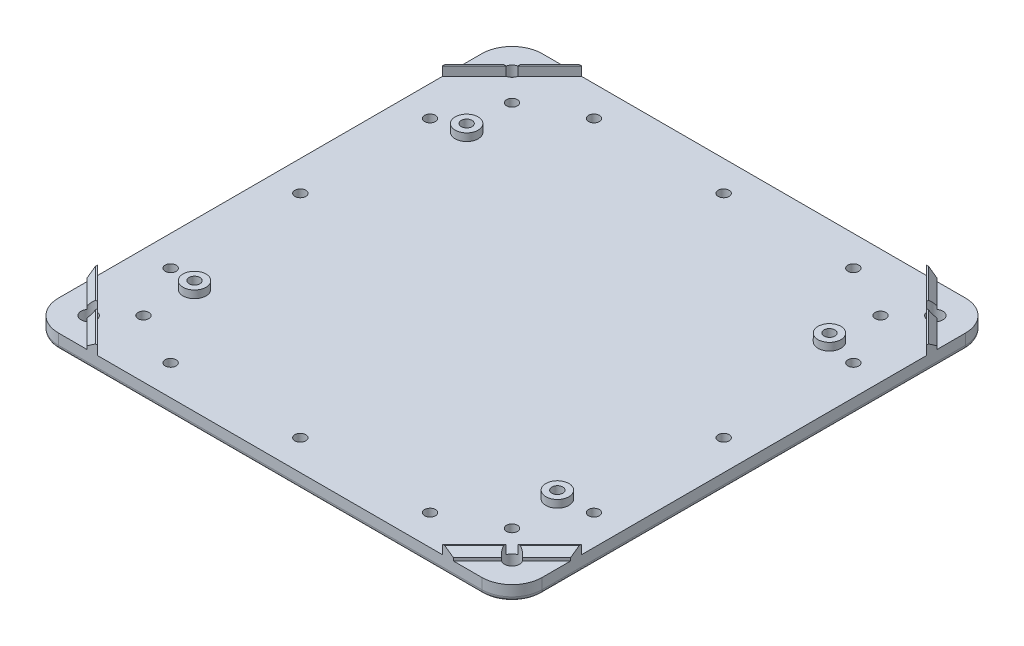
SolidWorks part; units mm, degrees
ref_plane "Front Plane" through (0, 0, 0) normal (0, 0, 1) x (1, 0, 0)
ref_plane "Top Plane" through (0, 0, 0) normal (0, 1, 0) x (1, 0, 0)
ref_plane "Right Plane" through (0, 0, 0) normal (1, 0, 0) x (0, 0, -1)
sketch "Sketch1" plane through (0, 0, 0) normal (0, 1, 0) x (1, 0, 0)
  line L1 (0, 0) -> (203.2, 0)
  line L2 (0, 0) -> (0, 203.2)
  line L3 (0, 203.2) -> (203.2, 203.2)
  line L4 (203.2, 0) -> (203.2, 203.2)
  dimension "D1" = 203.2
  dimension "D2" = 203.2
extrude "Boss-Extrude1" add sketch "Sketch1" along normal blind 6.35
fillet "Fillet1" radius 12.7 4 edges at (0, 3.175, -203.2) (0, 3.175, 0) (203.2, 3.175, 0) (203.2, 3.175, -203.2)
sketch "Sketch2" plane through (0, 0, 0) normal (0, -1, 0) x (1, 0, 0)
  circle A0 centre (12.7, -12.7) radius 3.175
  circle A1 centre (190.5, -12.7) radius 3.175
  circle A2 centre (190.5, -190.5) radius 3.175
  circle A3 centre (12.7, -190.5) radius 3.175
  arc A4 (190.5, -203.2) -> (203.2, -190.5) centre (190.5, -190.5) ccw construction
  arc A5 (12.7, 0) -> (0, -12.7) centre (12.7, -12.7) ccw construction
  arc A6 (12.7, 0) -> (0, -12.7) centre (12.7, -12.7) ccw construction
  dimension "D1" = 6.35
  dimension "D2" = 9.525
extrude "Cut-Extrude1" cut sketch "Sketch2" against normal through all
fillet "Fillet2" radius 1.905 12 edges at (3.7197, 0, -3.7197) (101.6, 0, 0) (199.4803, 0, -3.7197) (203.2, 0, -101.6) (199.4803, 0, -199.4803) (101.6, 0, -203.2) (3.7197, 0, -199.4803) (0, 0, -101.6) (12.7, 0, -15.875) (190.5, 0, -15.875) (190.5, 0, -193.675) (12.7, 0, -193.675)
sketch "Sketch3" plane through (0, 6.35, 0) normal (0, 1, 0) x (1, 0, 0)
  line L0 (3.7197, 3.7197) -> (24.1978, 24.1978) construction
  line L1 (24.1978, 24.1978) -> (0, 24.1978) construction
  line L2 (0, 190.5) -> (0, 12.7) construction
  line L3 (24.1978, 24.1978) -> (24.1978, 0) construction
  line L4 (12.7, 0) -> (190.5, 0) construction
  line L5 (3.7197, 199.4803) -> (24.1978, 179.0022) construction
  line L6 (0, 179.0022) -> (24.1978, 179.0022) construction
  line L7 (24.1978, 179.0022) -> (24.1978, 203.2) construction
  line L8 (190.5, 203.2) -> (12.7, 203.2) construction
  line L9 (199.4803, 3.7197) -> (179.0022, 24.1978) construction
  line L10 (179.0022, 24.1978) -> (179.0022, 0) construction
  line L12 (179.0022, 24.1978) -> (203.2, 24.1978) construction
  line L13 (203.2, 12.7) -> (203.2, 190.5) construction
  line L14 (199.4803, 199.4803) -> (179.0022, 179.0022) construction
  line L15 (179.0022, 179.0022) -> (203.2, 179.0022) construction
  line L16 (179.0022, 179.0022) -> (179.0022, 203.2) construction
  arc A0 (0, 12.7) -> (12.7, 0) centre (12.7, 12.7) ccw construction
  circle A1 centre (24.1978, 24.1978) radius 2.286
  arc A2 (190.5, 0) -> (203.2, 12.7) centre (190.5, 12.7) ccw construction
  arc A3 (203.2, 190.5) -> (190.5, 203.2) centre (190.5, 190.5) ccw construction
  arc A10 (12.7, 203.2) -> (0, 190.5) centre (12.7, 190.5) ccw construction
  circle A13 centre (179.0022, 179.0022) radius 2.286
  circle A14 centre (179.0022, 24.1978) radius 2.286
  circle A15 centre (24.1978, 179.0022) radius 2.286
  point P20 (101.6, 101.6)
  dimension "D2" = 4.572
  dimension "D1" = 28.9603
extrude "Cut-Extrude2" cut sketch "Sketch3" against normal through all
sketch "Sketch4" plane through (0, 6.35, 0) normal (0, 1, 0) x (1, 0, 0)
  line L0 (0, 190.5) -> (0, 12.7) construction
  line L1 (203.2, 12.7) -> (203.2, 190.5) construction
  line L2 (12.7, 0) -> (190.5, 0) construction
  line L3 (3.7197, 3.7197) -> (199.4803, 199.4803) construction
  circle A0 centre (47.117, 12.7) radius 2.286
  circle A1 centre (156.083, 12.7) radius 2.286
  arc A2 (0, 12.7) -> (12.7, 0) centre (12.7, 12.7) ccw construction
  arc A3 (203.2, 190.5) -> (190.5, 203.2) centre (190.5, 190.5) ccw construction
  circle A4 centre (12.7, 156.083) radius 2.286
  circle A5 centre (12.7, 47.117) radius 2.286
  circle A6 centre (156.083, 190.5) radius 2.286
  circle A7 centre (47.117, 190.5) radius 2.286
  circle A8 centre (190.5, 47.117) radius 2.286
  circle A9 centre (190.5, 156.083) radius 2.286
  circle A10 centre (101.6, 12.7) radius 2.286
  circle A11 centre (12.7, 101.6) radius 2.286
  circle A12 centre (101.6, 190.5) radius 2.286
  circle A13 centre (190.5, 101.6) radius 2.286
  point P18 (101.6, 101.6)
  dimension "D4" = 4.572
  dimension "D1" = 47.117
  dimension "D2" = 47.117
  dimension "D3" = 12.7
  dimension "D6" = 104.267
  dimension "D7" = 34.417
  dimension "D8" = 54.483
  dimension "D5" = 4
extrude "Cut-Extrude3" cut sketch "Sketch4" against normal through all
sketch "Sketch5" plane through (0, 6.35, 0) normal (0, 1, 0) x (1, 0, 0)
  line L0 (0, 190.5) -> (0, 12.7) construction
  line L1 (203.2, 12.7) -> (203.2, 190.5) construction
  line L2 (12.7, 0) -> (190.5, 0) construction
  line L3 (190.5, 203.2) -> (12.7, 203.2) construction
  circle A0 centre (25.4, 158.75) radius 2.286
  circle A1 centre (177.8, 158.75) radius 2.286
  circle A2 centre (177.8, 44.45) radius 2.286
  circle A3 centre (25.4, 44.45) radius 2.286
  circle A4 centre (25.4, 158.75) radius 4.826
  circle A5 centre (177.8, 158.75) radius 4.826
  circle A6 centre (177.8, 44.45) radius 4.826
  circle A7 centre (25.4, 44.45) radius 4.826
  dimension "D1" = 2.54
  dimension "D2" = 4.572
  dimension "D3" = 25.4
  dimension "D4" = 25.4
  dimension "D5" = 44.45
  dimension "D6" = 44.45
extrude "Boss-Extrude2" add sketch "Sketch5" along normal blind 3.175
sketch "Sketch6" plane through (0, 6.35, 0) normal (0, 1, 0) x (1, 0, 0)
  line L0 (203.2, 29.1287) -> (189.8864, 15.8151)
  line L1 (203.2, 12.7) -> (203.2, 190.5) construction
  line L2 (12.7, 0) -> (190.5, 0) construction
  line L3 (203.2, 29.1287) -> (203.2, 24.6386)
  line L4 (203.2, 24.6386) -> (193.0933, 14.5318)
  line L5 (178.5614, 0) -> (174.0713, 0)
  line L6 (187.3849, 13.3136) -> (174.0713, 0)
  line L7 (188.6682, 10.1067) -> (178.5614, 0)
  line L8 (3.7197, 3.7197) -> (199.4803, 199.4803) construction
  line L9 (13.3136, 15.8151) -> (0, 29.1287)
  line L10 (0, 24.6386) -> (0, 29.1287)
  line L11 (10.1067, 14.5318) -> (0, 24.6386)
  line L12 (24.6386, 0) -> (14.5318, 10.1067)
  line L13 (29.1287, 0) -> (15.8151, 13.3136)
  line L14 (29.1287, 0) -> (24.6386, 0)
  line L15 (15.8151, 189.8864) -> (29.1287, 203.2)
  line L16 (24.6386, 203.2) -> (29.1287, 203.2)
  line L17 (14.5318, 193.0933) -> (24.6386, 203.2)
  line L18 (0, 178.5614) -> (10.1067, 188.6682)
  line L19 (0, 174.0713) -> (13.3136, 187.3849)
  line L20 (0, 174.0713) -> (0, 178.5614)
  line L21 (189.8864, 187.3849) -> (203.2, 174.0713)
  line L22 (203.2, 178.5614) -> (203.2, 174.0713)
  line L23 (193.0933, 188.6682) -> (203.2, 178.5614)
  line L24 (178.5614, 203.2) -> (188.6682, 193.0933)
  line L25 (174.0713, 203.2) -> (187.3849, 189.8864)
  line L26 (174.0713, 203.2) -> (178.5614, 203.2)
  arc A0 (187.3849, 13.3136) -> (188.6682, 10.1067) centre (190.5, 12.7) ccw
  arc A1 (193.0933, 14.5318) -> (189.8864, 15.8151) centre (190.5, 12.7) ccw
  arc A2 (0, 12.7) -> (12.7, 0) centre (12.7, 12.7) ccw construction
  arc A3 (203.2, 190.5) -> (190.5, 203.2) centre (190.5, 190.5) ccw construction
  arc A4 (13.3136, 15.8151) -> (10.1067, 14.5318) centre (12.7, 12.7) ccw
  arc A5 (14.5318, 10.1067) -> (15.8151, 13.3136) centre (12.7, 12.7) ccw
  arc A6 (15.8151, 189.8864) -> (14.5318, 193.0933) centre (12.7, 190.5) ccw
  arc A7 (10.1067, 188.6682) -> (13.3136, 187.3849) centre (12.7, 190.5) ccw
  arc A8 (189.8864, 187.3849) -> (193.0933, 188.6682) centre (190.5, 190.5) ccw
  arc A9 (188.6682, 193.0933) -> (187.3849, 189.8864) centre (190.5, 190.5) ccw
  point P22 (101.6, 101.6)
  dimension "D4" = 6.35
  dimension "D1" = 29.1287
  dimension "D2" = 29.1287
  dimension "D3" = 3.175
  dimension "D6" = 177.8
  dimension "D5" = 4
extrude "Boss-Extrude3" add sketch "Sketch6" along normal blind 3.81
chamfer "Chamfer1" distance 2.54 angle 45 8 edges at (198.1466, 10.16, -19.5852) (183.6148, 10.16, -5.0534) (198.1466, 10.16, -183.6148) (183.6148, 10.16, -198.1466) (19.5852, 10.16, -198.1466) (5.0534, 10.16, -183.6148) (19.5852, 10.16, -5.0534) (5.0534, 10.16, -19.5852)
